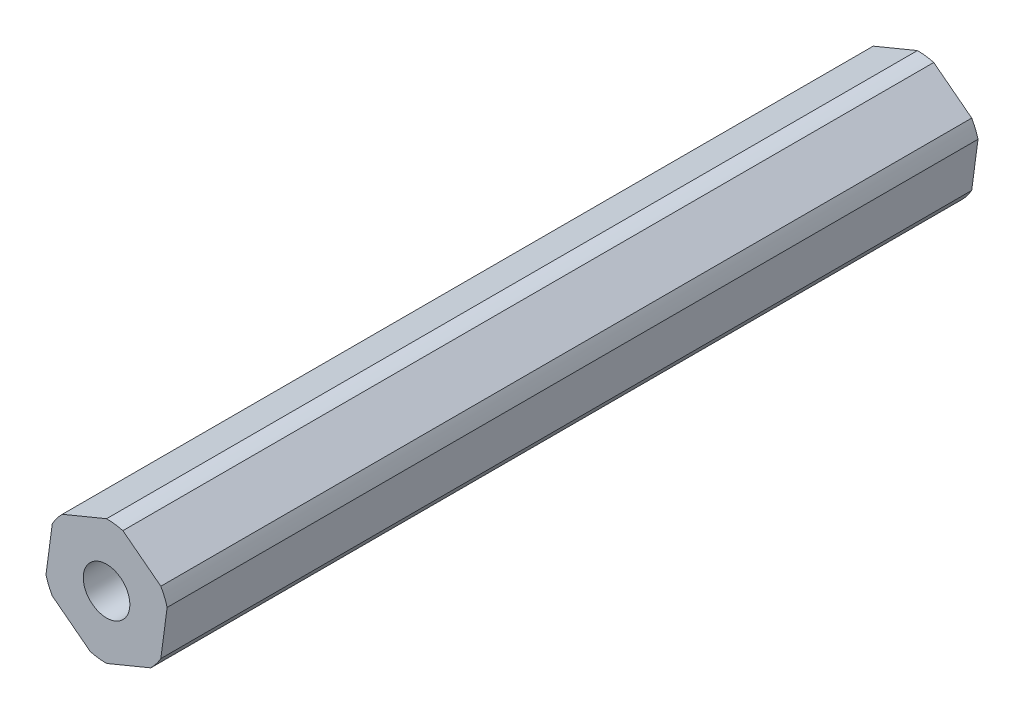
SolidWorks part; units mm, degrees
material "6061-T6 (SS)"
ref_plane "Front Plane" through (0, 0, 0) normal (0, 0, 1) x (1, 0, 0)
ref_plane "Top Plane" through (0, 0, 0) normal (0, 1, 0) x (1, 0, 0)
ref_plane "Right Plane" through (0, 0, 0) normal (1, 0, 0) x (0, 0, -1)
sketch "Sketch1" plane through (0, 0, 0) normal (0, 0, 1) x (1, 0, 0)
  line L1 (5.9502, 3.4353) -> (1.7899, 6.6335)
  line L2 (0, 6.8707) -> (-4.8498, 4.8668)
  line L3 (-5.9502, 3.4353) -> (-6.6397, -1.7666)
  line L4 (-5.9502, -3.4354) -> (-1.7899, -6.6335)
  line L5 (0, -6.8707) -> (4.8498, -4.8668)
  line L6 (5.9502, -3.4354) -> (6.6397, 1.7666)
  circle A0 centre (0, 0) radius 6.35 construction
  arc A1 (1.7899, 6.6335) -> (0, 6.8707) centre (0, 0) ccw
  arc A2 (6.6397, 1.7666) -> (5.9502, 3.4353) centre (0, 0) ccw
  arc A3 (4.8498, -4.8668) -> (5.9502, -3.4354) centre (0, 0) ccw
  arc A4 (-1.7899, -6.6335) -> (0, -6.8707) centre (0, 0) ccw
  arc A5 (-6.6397, -1.7666) -> (-5.9502, -3.4354) centre (0, 0) ccw
  arc A6 (-4.8498, 4.8668) -> (-5.9502, 3.4353) centre (0, 0) ccw
  dimension "D1" = 13.7414
  dimension ".5" = 12.7
extrude "Boss-Extrude1" add sketch "Sketch1" along normal blind 88.9
hole_wizard "1/4-20 Tapped Hole1" positions "Sketch3" profile "Sketch4" tap size "1/4-20" standard "ANSI Inch"
sketch "Sketch3" plane through (0, 0, 88.9) normal (0, 0, 1) x (1, 0, 0)
  point P0 (0, 0)
sketch "Sketch4" plane through (0, 0, 88.9) normal (1, 0, 0) x (0, -1, 0)
  line L0 (0, 0) -> (0, 18.0438)
  line L1 (0, 18.0438) -> (2.5527, 16.51)
  line L2 (2.5527, 16.51) -> (2.5527, 0)
  line L5 (2.5527, 0) -> (0, 0)
  line L10 (0, 18.0438) -> (-2.5527, 16.51) construction
  line L11 (0, -6.35) -> (0, 107.95) construction
  dimension "Tap Drill Dia." = 5.1054
  dimension "Tap Drill Depth" = 16.51
  dimension "Drill Angle" = 118
cosmetic thread "Hole Thread1"
hole_wizard "1/4-20 Tapped Hole2" positions "Sketch6" profile "Sketch5" tap size "1/4-20" standard "ANSI Inch"
sketch "Sketch6" plane through (0, 0, 0) normal (0, 0, -1) x (-1, 0, 0)
  point P0 (0, 0)
sketch "Sketch5" plane through (0, 0, 0) normal (1, 0, 0) x (0, 1, 0)
  line L0 (0, 0) -> (0, 18.0438)
  line L1 (0, 18.0438) -> (2.5527, 16.51)
  line L2 (2.5527, 16.51) -> (2.5527, 0)
  line L5 (2.5527, 0) -> (0, 0)
  line L10 (0, 18.0438) -> (-2.5527, 16.51) construction
  line L11 (0, -6.35) -> (0, 107.95) construction
  dimension "Tap Drill Dia." = 5.1054
  dimension "Tap Drill Depth" = 16.51
  dimension "Drill Angle" = 118
cosmetic thread "Hole Thread2" parameters "D1"=12.7, "D2"=6.35
